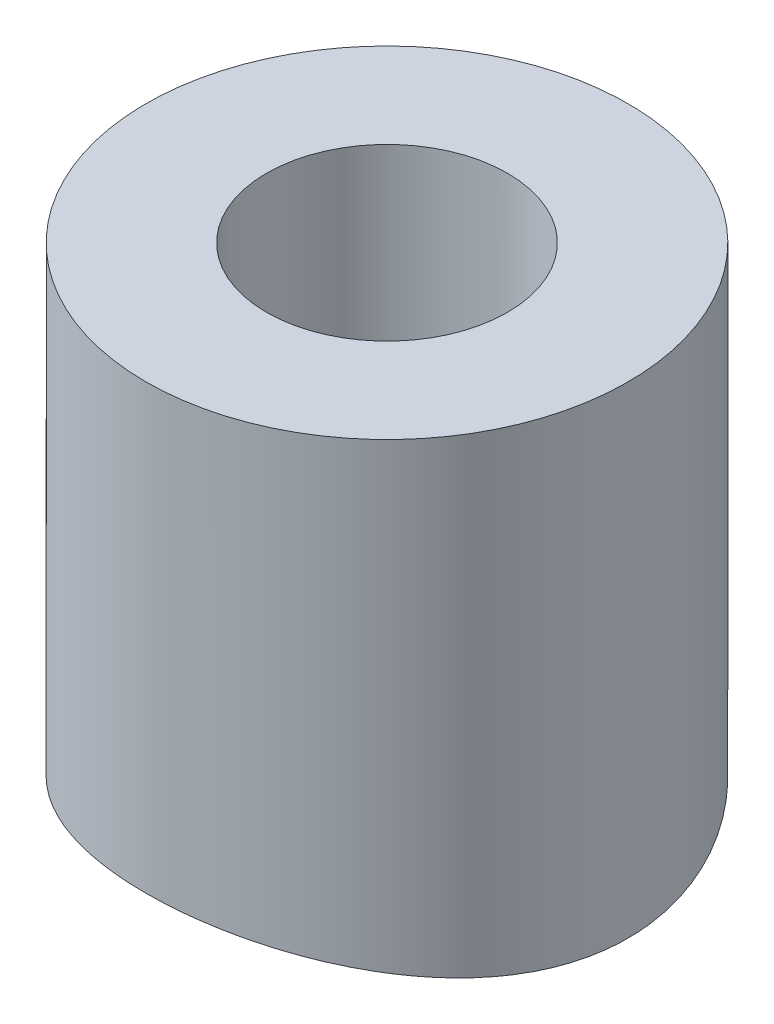
SolidWorks part; units mm, degrees
ref_plane "Front Plane" through (0, 0, 0) normal (0, 0, 1) x (1, 0, 0)
ref_plane "Top Plane" through (0, 0, 0) normal (0, 1, 0) x (1, 0, 0)
ref_plane "Right Plane" through (0, 0, 0) normal (1, 0, 0) x (0, 0, -1)
sketch "Sketch1" plane through (0, 0, 0) normal (0, 1, 0) x (1, 0, 0)
  circle A0 centre (0, 0) radius 2
  circle A1 centre (0, 0) radius 4
  dimension "D1" = 8
  dimension "D2" = 4
extrude "Boss-Extrude1" add sketch "Sketch1" along normal blind 7.35 and the other way blind 3
sketch "Sketch2" plane through (0, 0, 0) normal (0, 0, 1) x (1, 0, 0)
  line L0 (0, 0) -> (0, -12.7) construction
  circle A0 centre (0, -12.7) radius 12.7
  point P4 (0, -13.1711)
  dimension "D1" = 25.4
extrude "Cut-Extrude1" cut sketch "Sketch2" against normal blind 13 and the other way blind 13
